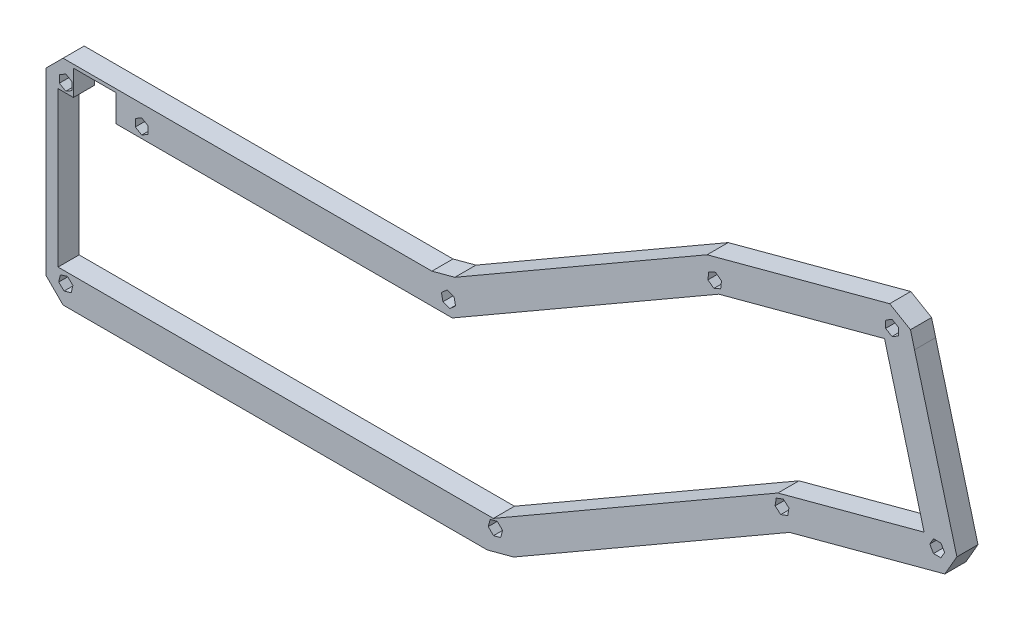
SolidWorks part; units mm, degrees
ref_plane "Plan de face" through (0, 0, 0) normal (0, 0, 1) x (1, 0, 0)
ref_plane "Plan de dessus" through (0, 0, 0) normal (0, 1, 0) x (1, 0, 0)
ref_plane "Plan de droite" through (0, 0, 0) normal (1, 0, 0) x (0, 0, -1)
sketch "Esquisse1" plane through (0, 0, 0) normal (0, 0, 1) x (1, 0, 0)
  line L0 (-73.9886, 18.0851) -> (-59.9886, 18.0851) construction
  line L1 (-73.9886, 37.0851) -> (-59.9886, 37.0851) construction
  line L2 (-73.9886, 37.0851) -> (-73.9886, 23.0851) construction
  line L3 (-73.9886, 23.0851) -> (-59.9886, 23.0851) construction
  line L4 (-59.9886, 37.0851) -> (-59.9886, 23.0851) construction
  line L5 (-73.9886, 18.0851) -> (-73.9886, 4.0851) construction
  line L6 (-73.9886, 4.0851) -> (-59.9886, 4.0851) construction
  line L7 (-59.9886, 18.0851) -> (-59.9886, 4.0851) construction
  line L8 (-73.9886, -0.9149) -> (-59.9886, -0.9149) construction
  line L9 (-73.9886, -0.9149) -> (-73.9886, -14.9149) construction
  line L10 (-73.9886, -14.9149) -> (-59.9886, -14.9149) construction
  line L11 (-59.9886, -0.9149) -> (-59.9886, -14.9149) construction
  line L12 (-73.9886, 37.0851) -> (-73.9886, 18.0851) construction
  line L13 (-54.9886, 18.0851) -> (-40.9886, 18.0851) construction
  line L14 (-54.9886, 37.0851) -> (-40.9886, 37.0851) construction
  line L15 (-54.9886, 37.0851) -> (-54.9886, 23.0851) construction
  line L16 (-54.9886, 23.0851) -> (-40.9886, 23.0851) construction
  line L17 (-40.9886, 37.0851) -> (-40.9886, 23.0851) construction
  line L18 (-54.9886, 18.0851) -> (-54.9886, 4.0851) construction
  line L19 (-54.9886, 4.0851) -> (-40.9886, 4.0851) construction
  line L20 (-40.9886, 18.0851) -> (-40.9886, 4.0851) construction
  line L21 (-54.9886, -0.9149) -> (-40.9886, -0.9149) construction
  line L22 (-54.9886, -0.9149) -> (-54.9886, -14.9149) construction
  line L23 (-54.9886, -14.9149) -> (-40.9886, -14.9149) construction
  line L24 (-40.9886, -0.9149) -> (-40.9886, -14.9149) construction
  line L25 (-54.9886, 37.0851) -> (-54.9886, 18.0851) construction
  line L26 (-35.9886, 18.0851) -> (-21.9886, 18.0851) construction
  line L27 (-35.9886, 37.0851) -> (-21.9886, 37.0851) construction
  line L28 (-35.9886, 37.0851) -> (-35.9886, 23.0851) construction
  line L29 (-35.9886, 23.0851) -> (-21.9886, 23.0851) construction
  line L30 (-21.9886, 37.0851) -> (-21.9886, 23.0851) construction
  line L31 (-35.9886, 18.0851) -> (-35.9886, 4.0851) construction
  line L32 (-35.9886, 4.0851) -> (-21.9886, 4.0851) construction
  line L33 (-21.9886, 18.0851) -> (-21.9886, 4.0851) construction
  line L34 (-35.9886, -0.9149) -> (-21.9886, -0.9149) construction
  line L35 (-35.9886, -0.9149) -> (-35.9886, -14.9149) construction
  line L36 (-35.9886, -14.9149) -> (-21.9886, -14.9149) construction
  line L37 (-21.9886, -0.9149) -> (-21.9886, -14.9149) construction
  line L38 (-35.9886, 37.0851) -> (-35.9886, 18.0851) construction
  line L39 (-16.9886, 18.0851) -> (-2.9886, 18.0851) construction
  line L40 (-16.9886, 37.0851) -> (-2.9886, 37.0851) construction
  line L41 (-16.9886, 37.0851) -> (-16.9886, 23.0851) construction
  line L42 (-16.9886, 23.0851) -> (-2.9886, 23.0851) construction
  line L43 (-2.9886, 37.0851) -> (-2.9886, 23.0851) construction
  line L44 (-16.9886, 18.0851) -> (-16.9886, 4.0851) construction
  line L45 (-16.9886, 4.0851) -> (-2.9886, 4.0851) construction
  line L46 (-2.9886, 18.0851) -> (-2.9886, 4.0851) construction
  line L47 (-16.9886, -0.9149) -> (-2.9886, -0.9149) construction
  line L48 (-16.9886, -0.9149) -> (-16.9886, -14.9149) construction
  line L49 (-16.9886, -14.9149) -> (-2.9886, -14.9149) construction
  line L50 (-2.9886, -0.9149) -> (-2.9886, -14.9149) construction
  line L51 (-16.9886, 37.0851) -> (-16.9886, 18.0851) construction
  line L52 (2.0114, 18.0851) -> (16.0114, 18.0851) construction
  line L53 (2.0114, 37.0851) -> (16.0114, 37.0851) construction
  line L54 (2.0114, 37.0851) -> (2.0114, 23.0851) construction
  line L55 (2.0114, 23.0851) -> (16.0114, 23.0851) construction
  line L56 (16.0114, 37.0851) -> (16.0114, 23.0851) construction
  line L57 (2.0114, 18.0851) -> (2.0114, 4.0851) construction
  line L58 (2.0114, 4.0851) -> (16.0114, 4.0851) construction
  line L59 (16.0114, 18.0851) -> (16.0114, 4.0851) construction
  line L60 (2.0114, -0.9149) -> (16.0114, -0.9149) construction
  line L61 (2.0114, -0.9149) -> (2.0114, -14.9149) construction
  line L62 (2.0114, -14.9149) -> (16.0114, -14.9149) construction
  line L63 (16.0114, -0.9149) -> (16.0114, -14.9149) construction
  line L64 (2.0114, 37.0851) -> (2.0114, 18.0851) construction
  line L65 (21.0114, 18.0851) -> (35.0114, 18.0851) construction
  line L66 (21.0114, 37.0851) -> (35.0114, 37.0851) construction
  line L67 (21.0114, 37.0851) -> (21.0114, 23.0851) construction
  line L68 (21.0114, 23.0851) -> (35.0114, 23.0851) construction
  line L69 (35.0114, 37.0851) -> (35.0114, 23.0851) construction
  line L70 (21.0114, 18.0851) -> (21.0114, 4.0851) construction
  line L71 (21.0114, 4.0851) -> (35.0114, 4.0851) construction
  line L72 (35.0114, 18.0851) -> (35.0114, 4.0851) construction
  line L73 (21.0114, -0.9149) -> (35.0114, -0.9149) construction
  line L74 (21.0114, -0.9149) -> (21.0114, -14.9149) construction
  line L75 (21.0114, -14.9149) -> (35.0114, -14.9149) construction
  line L76 (35.0114, -0.9149) -> (35.0114, -14.9149) construction
  line L77 (21.0114, 37.0851) -> (21.0114, 18.0851) construction
  line L78 (40.0114, 18.0851) -> (54.0114, 18.0851) construction
  line L79 (40.0114, 37.0851) -> (54.0114, 37.0851) construction
  line L80 (40.0114, 37.0851) -> (40.0114, 23.0851) construction
  line L81 (40.0114, 23.0851) -> (54.0114, 23.0851) construction
  line L82 (54.0114, 37.0851) -> (54.0114, 23.0851) construction
  line L83 (40.0114, 18.0851) -> (40.0114, 4.0851) construction
  line L84 (40.0114, 4.0851) -> (54.0114, 4.0851) construction
  line L85 (54.0114, 18.0851) -> (54.0114, 4.0851) construction
  line L86 (40.0114, -0.9149) -> (54.0114, -0.9149) construction
  line L87 (40.0114, -0.9149) -> (40.0114, -14.9149) construction
  line L88 (40.0114, -14.9149) -> (54.0114, -14.9149) construction
  line L89 (54.0114, -0.9149) -> (54.0114, -14.9149) construction
  line L90 (40.0114, 37.0851) -> (40.0114, 18.0851) construction
  line L91 (-73.9886, 18.0851) -> (-54.9886, 18.0851) construction
  line L92 (56.0114, 20.0851) -> (56.7532, 18.8002) construction
  line L93 (38.0114, 39.0851) -> (56.0114, 39.0851) construction
  line L94 (56.0114, 39.0851) -> (56.0114, 21.0851) construction
  line L95 (38.0114, 21.0851) -> (56.0114, 21.0851) construction
  line L96 (38.0114, 39.0851) -> (38.0114, 21.0851) construction
  line L97 (19.0114, 39.0851) -> (37.0114, 39.0851) construction
  line L98 (37.0114, 39.0851) -> (37.0114, 21.0851) construction
  line L99 (19.0114, 21.0851) -> (37.0114, 21.0851) construction
  line L100 (19.0114, 39.0851) -> (19.0114, 21.0851) construction
  line L101 (79.4363, 55.512) -> (88.4363, 39.9235) construction
  line L102 (88.4363, 39.9235) -> (72.8478, 30.9235) construction
  line L103 (63.8478, 46.512) -> (72.8478, 30.9235) construction
  line L104 (79.4363, 55.512) -> (63.8478, 46.512) construction
  line L105 (62.9818, 46.012) -> (71.9818, 30.4235) construction
  line L106 (71.9818, 30.4235) -> (56.3933, 21.4235) construction
  line L107 (47.3933, 37.012) -> (56.3933, 21.4235) construction
  line L108 (62.9818, 46.012) -> (47.3933, 37.012) construction
  line L109 (164.5845, 60.0309) -> (148.9961, 51.0309) construction
  line L110 (62.2497, 43.2799) -> (71.7497, 26.8254) construction
  line L111 (78.7042, 52.7799) -> (88.2042, 36.3254) construction
  line L112 (95.1587, 62.2799) -> (104.6587, 45.8254) construction
  line L113 (111.6132, 71.7799) -> (121.1132, 55.3254) construction
  line L114 (128.0677, 81.2799) -> (137.5677, 64.8254) construction
  line L115 (144.5221, 90.7799) -> (154.0221, 74.3254) construction
  line L116 (148.9961, 51.0309) -> (157.6657, 36.0146) construction
  line L117 (69.1254, 3.371) -> (76.1254, -8.7534) construction
  line L118 (88.2497, -1.7534) -> (76.1254, -8.7534) construction
  line L119 (81.2497, 10.371) -> (88.2497, -1.7534) construction
  line L120 (81.2497, 10.371) -> (69.1254, 3.371) construction
  line L121 (59.6254, 19.8254) -> (66.6254, 7.7011) construction
  line L122 (78.7497, 14.7011) -> (66.6254, 7.7011) construction
  line L123 (71.7497, 26.8254) -> (78.7497, 14.7011) construction
  line L124 (50.1254, 36.2799) -> (57.1254, 24.1556) construction
  line L125 (69.2497, 31.1556) -> (57.1254, 24.1556) construction
  line L126 (62.2497, 43.2799) -> (69.2497, 31.1556) construction
  line L127 (62.2497, 43.2799) -> (50.1254, 36.2799) construction
  line L128 (71.7497, 26.8254) -> (59.6254, 19.8254) construction
  line L129 (85.5799, 12.871) -> (92.5799, 0.7466) construction
  line L130 (104.7042, 7.7466) -> (92.5799, 0.7466) construction
  line L131 (97.7042, 19.871) -> (104.7042, 7.7466) construction
  line L132 (97.7042, 19.871) -> (85.5799, 12.871) construction
  line L133 (76.0799, 29.3254) -> (83.0799, 17.2011) construction
  line L134 (95.2042, 24.2011) -> (83.0799, 17.2011) construction
  line L135 (88.2042, 36.3254) -> (95.2042, 24.2011) construction
  line L136 (66.5799, 45.7799) -> (73.5799, 33.6556) construction
  line L137 (85.7042, 40.6556) -> (73.5799, 33.6556) construction
  line L138 (78.7042, 52.7799) -> (85.7042, 40.6556) construction
  line L139 (78.7042, 52.7799) -> (66.5799, 45.7799) construction
  line L140 (88.2042, 36.3254) -> (76.0799, 29.3254) construction
  line L141 (102.0343, 22.371) -> (109.0343, 10.2466) construction
  line L142 (121.1587, 17.2466) -> (109.0343, 10.2466) construction
  line L143 (114.1587, 29.371) -> (121.1587, 17.2466) construction
  line L144 (114.1587, 29.371) -> (102.0343, 22.371) construction
  line L145 (92.5343, 38.8254) -> (99.5343, 26.7011) construction
  line L146 (111.6587, 33.7011) -> (99.5343, 26.7011) construction
  line L147 (104.6587, 45.8254) -> (111.6587, 33.7011) construction
  line L148 (83.0343, 55.2799) -> (90.0343, 43.1556) construction
  line L149 (102.1587, 50.1556) -> (90.0343, 43.1556) construction
  line L150 (95.1587, 62.2799) -> (102.1587, 50.1556) construction
  line L151 (95.1587, 62.2799) -> (83.0343, 55.2799) construction
  line L152 (104.6587, 45.8254) -> (92.5343, 38.8254) construction
  line L153 (118.4888, 31.871) -> (125.4888, 19.7466) construction
  line L154 (137.6132, 26.7466) -> (125.4888, 19.7466) construction
  line L155 (130.6132, 38.871) -> (137.6132, 26.7466) construction
  line L156 (130.6132, 38.871) -> (118.4888, 31.871) construction
  line L157 (108.9888, 48.3254) -> (115.9888, 36.2011) construction
  line L158 (128.1132, 43.2011) -> (115.9888, 36.2011) construction
  line L159 (121.1132, 55.3254) -> (128.1132, 43.2011) construction
  line L160 (99.4888, 64.7799) -> (106.4888, 52.6556) construction
  line L161 (118.6132, 59.6556) -> (106.4888, 52.6556) construction
  line L162 (111.6132, 71.7799) -> (118.6132, 59.6556) construction
  line L163 (111.6132, 71.7799) -> (99.4888, 64.7799) construction
  line L164 (121.1132, 55.3254) -> (108.9888, 48.3254) construction
  line L165 (134.9433, 41.371) -> (141.9433, 29.2466) construction
  line L166 (154.0677, 36.2466) -> (141.9433, 29.2466) construction
  line L167 (147.0677, 48.371) -> (154.0677, 36.2466) construction
  line L168 (147.0677, 48.371) -> (134.9433, 41.371) construction
  line L169 (125.4433, 57.8254) -> (132.4433, 45.7011) construction
  line L170 (144.5677, 52.7011) -> (132.4433, 45.7011) construction
  line L171 (137.5677, 64.8254) -> (144.5677, 52.7011) construction
  line L172 (115.9433, 74.2799) -> (122.9433, 62.1556) construction
  line L173 (135.0677, 69.1556) -> (122.9433, 62.1556) construction
  line L174 (128.0677, 81.2799) -> (135.0677, 69.1556) construction
  line L175 (128.0677, 81.2799) -> (115.9433, 74.2799) construction
  line L176 (137.5677, 64.8254) -> (125.4433, 57.8254) construction
  line L177 (151.7281, 50.2988) -> (158.3978, 38.7466) construction
  line L178 (170.5221, 45.7466) -> (158.3978, 38.7466) construction
  line L179 (163.8525, 57.2988) -> (170.5221, 45.7466) construction
  line L180 (163.8525, 57.2988) -> (151.7281, 50.2988) construction
  line L181 (141.8978, 67.3254) -> (148.8978, 55.2011) construction
  line L182 (161.0221, 62.2011) -> (148.8978, 55.2011) construction
  line L183 (154.0221, 74.3254) -> (161.0221, 62.2011) construction
  line L184 (132.3978, 83.7799) -> (139.3978, 71.6556) construction
  line L185 (151.5221, 78.6556) -> (139.3978, 71.6556) construction
  line L186 (144.5221, 90.7799) -> (151.5221, 78.6556) construction
  line L187 (144.5221, 90.7799) -> (132.3978, 83.7799) construction
  line L188 (154.0221, 74.3254) -> (141.8978, 67.3254) construction
  line L189 (173.2542, 45.0146) -> (157.6657, 36.0146) construction
  line L190 (164.5845, 60.0309) -> (173.2542, 45.0146) construction
  line L191 (178.3169, 34.0986) -> (169.0534, 56.4627) construction
  line L192 (169.6903, 62.1458) -> (174.1781, 45.3972) construction
  line L193 (174.1781, 45.3972) -> (191.5647, 50.056) construction
  line L194 (187.077, 66.8045) -> (191.5647, 50.056) construction
  line L195 (162.1337, 98.0749) -> (167.0513, 79.7223) construction
  line L196 (169.6903, 62.1458) -> (187.077, 66.8045) construction
  line L197 (167.0513, 79.7223) -> (180.5742, 83.3457) construction
  line L198 (162.1337, 98.0749) -> (175.6567, 101.6983) construction
  line L199 (162.1337, 98.0749) -> (165.7572, 84.5519) construction
  line L200 (165.7572, 84.5519) -> (179.2801, 88.1754) construction
  line L201 (175.6567, 101.6983) -> (179.2801, 88.1754) construction
  line L202 (167.0513, 79.7223) -> (170.6747, 66.1993) construction
  line L203 (170.6747, 66.1993) -> (184.1977, 69.8228) construction
  line L204 (180.5742, 83.3457) -> (184.1977, 69.8228) construction
  line L205 (172.1398, 60.7315) -> (185.6628, 64.355) construction
  line L206 (172.1398, 60.7315) -> (175.5923, 47.8467) construction
  line L207 (175.5923, 47.8467) -> (189.1152, 51.4702) construction
  line L208 (185.6628, 64.355) -> (189.1152, 51.4702) construction
  line L209 (185.4038, 84.6398) -> (198.9268, 88.2633) construction
  line L210 (180.4863, 102.9924) -> (194.0092, 106.6159) construction
  line L211 (180.4863, 102.9924) -> (184.1097, 89.4695) construction
  line L212 (184.1097, 89.4695) -> (197.6327, 93.0929) construction
  line L213 (194.0092, 106.6159) -> (197.6327, 93.0929) construction
  line L214 (185.4038, 84.6398) -> (189.0273, 71.1169) construction
  line L215 (189.0273, 71.1169) -> (202.5503, 74.7403) construction
  line L216 (198.9268, 88.2633) -> (202.5503, 74.7403) construction
  line L217 (190.4924, 65.6491) -> (204.0154, 69.2726) construction
  line L218 (190.4924, 65.6491) -> (193.9449, 52.7643) construction
  line L219 (193.9449, 52.7643) -> (207.4678, 56.3878) construction
  line L220 (204.0154, 69.2726) -> (207.4678, 56.3878) construction
  line L221 (188.0429, 67.0633) -> (192.5307, 50.3148) construction
  line L222 (192.5307, 50.3148) -> (209.9173, 54.9735) construction
  line L223 (205.4296, 71.7221) -> (209.9173, 54.9735) construction
  line L224 (180.4863, 102.9924) -> (185.4038, 84.6398) construction
  line L225 (188.0429, 67.0633) -> (205.4296, 71.7221) construction
  line L226 (203.7564, 89.5574) -> (217.2794, 93.1809) construction
  line L227 (198.8389, 107.91) -> (212.3618, 111.5335) construction
  line L228 (198.8389, 107.91) -> (202.4623, 94.387) construction
  line L229 (202.4623, 94.387) -> (215.9853, 98.0105) construction
  line L230 (212.3618, 111.5335) -> (215.9853, 98.0105) construction
  line L231 (203.7564, 89.5574) -> (207.3799, 76.0344) construction
  line L232 (207.3799, 76.0344) -> (220.9029, 79.6579) construction
  line L233 (217.2794, 93.1809) -> (220.9029, 79.6579) construction
  line L234 (208.845, 70.5667) -> (222.368, 74.1901) construction
  line L235 (208.845, 70.5667) -> (212.2975, 57.6819) construction
  line L236 (212.2975, 57.6819) -> (225.8204, 61.3053) construction
  line L237 (222.368, 74.1901) -> (225.8204, 61.3053) construction
  line L238 (206.3955, 71.9809) -> (210.8833, 55.2324) construction
  line L239 (210.8833, 55.2324) -> (228.2699, 59.8911) construction
  line L240 (223.7822, 76.6396) -> (228.2699, 59.8911) construction
  line L241 (198.8389, 107.91) -> (203.7564, 89.5574) construction
  line L242 (206.3955, 71.9809) -> (223.7822, 76.6396) construction
  line L243 (167.0513, 79.7223) -> (185.4038, 84.6398) construction
  line L244 (38.0114, 20.0851) -> (56.0114, 20.0851) construction
  line L245 (56.0114, 20.0851) -> (56.0114, 2.0851) construction
  line L246 (38.0114, 2.0851) -> (56.0114, 2.0851) construction
  line L247 (38.0114, 20.0851) -> (38.0114, 2.0851) construction
  line L248 (72.4818, 29.5575) -> (56.8933, 20.5575) construction
  line L249 (56.8933, 20.5575) -> (65.8933, 4.969) construction
  line L250 (81.4818, 13.969) -> (65.8933, 4.969) construction
  line L251 (72.4818, 29.5575) -> (81.4818, 13.969) construction
  line L252 (56.8933, 20.5575) -> (57.6111, 19.3142) construction
  line L253 (164.6018, 81.1365) -> (169.2605, 63.7498) construction
  line L254 (169.2605, 63.7498) -> (186.6472, 68.4086) construction
  line L255 (181.9884, 85.7952) -> (186.6472, 68.4086) construction
  line L256 (164.6018, 81.1365) -> (181.9884, 85.7952) construction
  line L257 (154.7542, 77.0575) -> (163.7542, 61.469) construction
  line L258 (163.7542, 61.469) -> (148.1657, 52.469) construction
  line L259 (139.1657, 68.0575) -> (148.1657, 52.469) construction
  line L260 (154.7542, 77.0575) -> (139.1657, 68.0575) construction
  line L261 (196.3894, 109.3242) -> (213.776, 113.983) construction
  line L262 (-94.7538, 35.7952) -> (-76.7538, 35.7952) construction
  line L263 (-94.7538, 35.7952) -> (-94.7538, 2.7952) construction
  line L264 (-94.7538, 2.7952) -> (-76.7538, 2.7952) construction
  line L265 (-76.7538, 35.7952) -> (-76.7538, 2.7952) construction
  line L266 (213.776, 113.983) -> (218.4348, 96.5963) construction
  line L267 (201.0481, 91.9375) -> (218.4348, 96.5963) construction
  line L268 (196.3894, 109.3242) -> (201.0481, 91.9375) construction
  line L269 (-75.9886, -16.9149) -> (-57.9886, -16.9149) construction
  line L270 (-57.9886, 1.0851) -> (-57.9886, -16.9149) construction
  line L271 (-75.9886, 1.0851) -> (-57.9886, 1.0851) construction
  line L272 (-75.9886, 1.0851) -> (-75.9886, -16.9149) construction
  line L273 (38.0114, -16.9149) -> (56.0114, -16.9149) construction
  line L274 (56.0114, 1.0851) -> (56.0114, -16.9149) construction
  line L275 (38.0114, 1.0851) -> (56.0114, 1.0851) construction
  line L276 (38.0114, 1.0851) -> (38.0114, -16.9149) construction
  line L277 (-75.9886, 39.0851) -> (-57.9886, 39.0851) construction
  line L278 (-57.9886, 39.0851) -> (-57.9886, 21.0851) construction
  line L279 (-75.9886, 21.0851) -> (-57.9886, 21.0851) construction
  line L280 (-75.9886, 39.0851) -> (-75.9886, 21.0851) construction
  line L281 (145.2542, 93.512) -> (129.6657, 84.512) construction
  line L282 (129.6657, 84.512) -> (138.6657, 68.9235) construction
  line L283 (154.2542, 77.9235) -> (138.6657, 68.9235) construction
  line L284 (145.2542, 93.512) -> (154.2542, 77.9235) construction
  line L285 (223.4353, 116.5711) -> (228.0941, 99.1845) construction
  line L286 (148.2159, 106.7689) -> (211.1879, 123.6422) construction
  line L287 (177.5508, 35.9482) -> (235.6877, 51.5259) construction
  line L288 (177.5508, 35.9482) -> (72.9989, -24.4149) construction
  line L289 (-95.7538, -26.9149) -> (63.6687, -26.9149) construction
  line L290 (-100.7538, 35.7952) -> (-100.7538, -21.9149) construction
  line L291 (-75.9886, 49.0851) -> (43.3046, 49.0851) construction
  line L292 (148.2159, 106.7689) -> (52.6347, 51.5851) construction
  line L293 (-75.9886, 49.0851) -> (-57.9886, 49.0851) construction
  line L294 (140.2542, 102.1722) -> (124.6657, 93.1722) construction
  line L295 (193.8012, 118.9835) -> (211.1879, 123.6422) construction
  line L296 (213.4714, 45.5731) -> (230.8581, 50.2318) construction
  line L297 (38.0114, -26.9149) -> (38.0114, -85.4624) construction
  line L298 (178.2542, 36.3543) -> (162.6657, 27.3543) construction
  line L299 (38.0114, -26.9149) -> (56.0114, -26.9149) construction
  line L300 (-100.7538, 2.7952) -> (-100.7538, -38.0419) construction
  line L301 (-100.7538, 35.7952) -> (-100.7538, 2.7952) construction
  line L302 (-75.9886, 49.0851) -> (-95.7538, 49.0851) construction
  line L303 (-100.7538, 44.0851) -> (-100.7538, 35.7952) construction
  line L304 (211.1879, 123.6422) -> (216.0693, 124.9502) construction
  line L305 (222.1671, 121.4078) -> (223.4353, 116.5711) construction
  line L306 (228.0941, 99.1845) -> (239.2233, 57.6497) construction
  line L307 (216.0693, 124.9502) -> (222.1671, 121.4078) construction
  line L308 (235.6877, 51.5259) -> (239.2233, 57.6497) construction
  line L309 (63.6687, -26.9149) -> (72.9989, -24.4149) construction
  line L310 (52.6347, 51.5851) -> (43.3046, 49.0851) construction
  line L311 (-95.7538, 49.0851) -> (-100.7538, 44.0851) construction
  line L312 (-100.7538, -21.9149) -> (-95.7538, -26.9149) construction
  line L313 (-95.7538, 49.0851) -> (-95.7538, 44.0851) construction
  line L314 (-95.7538, 44.0851) -> (-100.7538, 44.0851) construction
  line L315 (-95.7538, -26.9149) -> (-95.7538, -21.9149) construction
  line L316 (68.3338, -25.6649) -> (67.0397, -20.8353) construction
  line L317 (47.9697, 50.3351) -> (49.2637, 45.5055) construction
  line L318 (177.5508, 35.9482) -> (175.6374, 40.5676) construction
  line L319 (148.2159, 106.7689) -> (150.1293, 102.1495) construction
  line L320 (239.2233, 57.6497) -> (234.4455, 56.3695) construction
  line L321 (216.0693, 124.9502) -> (217.3634, 120.1206) construction
  line L322 (-75.9886, 49.5851) -> (43.2388, 49.5851) construction
  line L323 (52.4417, 52.051) -> (43.2388, 49.5851) construction
  line L324 (148.0229, 107.2348) -> (52.4417, 52.051) construction
  line L325 (148.0229, 107.2348) -> (211.0584, 124.1252) construction
  line L326 (211.0584, 124.1252) -> (216.1407, 125.487) construction
  line L327 (216.1407, 125.487) -> (222.598, 121.7357) construction
  line L328 (222.598, 121.7357) -> (223.9186, 116.6993) construction
  line L329 (223.9186, 116.6993) -> (228.577, 99.3139) construction
  line L330 (228.577, 99.3139) -> (239.7598, 57.579) construction
  line L331 (236.0172, 51.0966) -> (239.7598, 57.579) construction
  line L332 (177.7438, 35.4823) -> (236.0172, 51.0966) construction
  line L333 (177.7438, 35.4823) -> (73.1918, -24.8808) construction
  line L334 (63.7346, -27.4149) -> (73.1918, -24.8808) construction
  line L335 (-95.9609, -27.4149) -> (63.7346, -27.4149) construction
  line L336 (-101.2538, -22.122) -> (-95.9609, -27.4149) construction
  line L337 (-101.2538, 35.7952) -> (-101.2538, -22.122) construction
  line L338 (-101.2538, 44.2922) -> (-101.2538, 35.7952) construction
  line L339 (-95.9609, 49.5851) -> (-101.2538, 44.2922) construction
  line L340 (-75.9886, 49.5851) -> (-76.7538, 49.5851) construction
  line L341 (2.0114, 40.0851) -> (52.7161, 40.0851)
  line L342 (151.6898, 98.3823) -> (50.7161, 40.0851)
  line L343 (-95.7538, 44.0851) -> (-63.3184, 44.0851) construction
  line L344 (-98.6986, -17.9149) -> (66.2572, -17.9149)
  line L345 (174.0769, 44.3349) -> (66.2572, -17.9149)
  line L346 (174.0769, 44.3349) -> (229.4947, 59.184)
  line L347 (214.4832, 115.2077) -> (229.4947, 59.184)
  line L348 (151.6898, 98.3823) -> (214.4832, 115.2077)
  line L349 (225.2657, 74.9666) -> (228.7182, 62.0818) construction
  line L350 (176.3687, 44.949) -> (189.8917, 48.5724) construction
  line L351 (89.7497, -4.3515) -> (77.6254, -11.3515) construction
  line L352 (-54.9886, -17.9149) -> (-40.9886, -17.9149) construction
  line L353 (-92.8618, 49.5851) -> (-76.7538, 49.5851) construction
  line L354 (2.0114, 40.0851) -> (16.0114, 40.0851) construction
  line L355 (77.2042, 55.378) -> (65.0799, 48.378) construction
  line L356 (179.7098, 105.8902) -> (193.2328, 109.5137) construction
  line L357 (2.0114, 40.0851) -> (-76.7538, 40.0851)
  line L358 (-76.7538, 40.0851) -> (-76.7538, 54.5851) construction
  line L359 (-92.8618, 54.5851) -> (-76.7538, 54.5851) construction
  line L360 (-98.6986, 40.6556) -> (-94.8608, 40.6556)
  line L361 (-94.8608, 40.6556) -> (-92.8618, 40.6556)
  line L362 (-94.8608, 49.5851) -> (-95.9609, 49.5851) construction
  line L363 (-66.9886, 37.0851) -> (-66.9886, 49.5851) construction
  line L364 (-75.9886, 49.5851) -> (-95.9609, 49.5851) construction
  line L365 (-92.8618, 40.6556) -> (-92.8618, 54.5851) construction
  line L366 (-76.7538, 39.0851) -> (-97.0101, 39.0851) construction
  line L367 (-76.7538, 39.0851) -> (-76.7538, 1.0851) construction
  line L368 (-76.7538, 1.0851) -> (-97.0101, 1.0851) construction
  line L369 (-97.0101, 39.0851) -> (-97.0101, 1.0851) construction
  line L370 (-92.8618, 49.5851) -> (-94.8608, 49.5851) construction
  line L371 (-98.6986, 40.6556) -> (-98.6986, -17.9149)
  line L372 (-75.9886, 54.5851) -> (-76.7538, 54.5851) construction
  line L373 (-75.9886, 54.5851) -> (42.5805, 54.5851) construction
  line L374 (50.5118, 56.7103) -> (42.5805, 54.5851) construction
  line L375 (146.093, 111.8941) -> (50.5118, 56.7103) construction
  line L376 (146.093, 111.8941) -> (209.7644, 128.9548) construction
  line L377 (209.7644, 128.9548) -> (216.8547, 130.8547) construction
  line L378 (216.8547, 130.8547) -> (226.9072, 125.0148) construction
  line L379 (226.9072, 125.0148) -> (228.7517, 117.9804) construction
  line L380 (228.7517, 117.9804) -> (233.4066, 100.608) construction
  line L381 (233.4066, 100.608) -> (245.1255, 56.8726) construction
  line L382 (239.3118, 46.803) -> (245.1255, 56.8726) construction
  line L383 (179.6737, 30.823) -> (239.3118, 46.803) construction
  line L384 (179.6737, 30.823) -> (75.1218, -29.5401) construction
  line L385 (64.3928, -32.4149) -> (75.1218, -29.5401) construction
  line L386 (-98.0319, -32.4149) -> (64.3928, -32.4149) construction
  line L387 (-106.2538, -24.1931) -> (-98.0319, -32.4149) construction
  line L388 (-106.2538, 35.7952) -> (-106.2538, -24.1931) construction
  line L389 (-106.2538, 46.3633) -> (-106.2538, 35.7952) construction
  line L390 (-98.0319, 54.5851) -> (-106.2538, 46.3633) construction
  line L391 (-94.8608, 54.5851) -> (-98.0319, 54.5851) construction
  line L392 (-92.8618, 54.5851) -> (-94.8608, 54.5851) construction
  line L393 (-92.8618, 50.2988) -> (-76.7538, 50.2988)
  line L394 (-76.7538, 54.5851) -> (-92.8618, 54.5851) construction
  line L395 (-76.7538, 51.5851) -> (-92.8618, 51.5851)
  line L396 (-92.8618, 51.5851) -> (-94.8608, 51.5851)
  line L397 (-94.8608, 51.5851) -> (-96.7893, 51.5851)
  line L398 (-96.7893, 51.5851) -> (-103.2538, 45.1206)
  line L399 (-103.2538, 45.1206) -> (-103.2538, 35.7952)
  line L400 (-103.2538, 35.7952) -> (-103.2538, -22.9504)
  line L401 (-103.2538, -22.9504) -> (-96.7893, -29.4149)
  line L402 (-96.7893, -29.4149) -> (63.9979, -29.4149)
  line L403 (63.9979, -29.4149) -> (73.9638, -26.7445)
  line L404 (178.5158, 33.6186) -> (73.9638, -26.7445)
  line L405 (178.5158, 33.6186) -> (237.335, 49.3791)
  line L406 (237.335, 49.3791) -> (241.9061, 57.2965)
  line L407 (230.5089, 99.8315) -> (241.9061, 57.2965)
  line L408 (225.8519, 117.2117) -> (230.5089, 99.8315)
  line L409 (224.3217, 123.0473) -> (225.8519, 117.2117)
  line L410 (216.4263, 127.634) -> (224.3217, 123.0473)
  line L411 (210.5408, 126.057) -> (216.4263, 127.634)
  line L412 (147.2509, 109.0986) -> (210.5408, 126.057)
  line L413 (147.2509, 109.0986) -> (51.6698, 53.9147)
  line L414 (51.6698, 53.9147) -> (42.9755, 51.5851)
  line L415 (-75.9886, 51.5851) -> (42.9755, 51.5851)
  line L416 (-75.9886, 51.5851) -> (-76.7538, 51.5851)
  line L417 (-76.7538, 48.6361) -> (-76.7538, 40.0851)
  line L418 (-92.8618, 48.6361) -> (-92.8618, 40.6556)
  line L419 (-76.7538, 50.2988) -> (-76.7538, 48.6361)
  line L420 (-92.8618, 50.2988) -> (-92.8618, 48.6361)
  line L421 (-97.4756, -23.6367) -> (-94.032, -20.1931) construction
  line L422 (-93.3188, 42.6793) -> (-93.3188, 45.491)
  line L423 (-93.3188, 45.491) -> (-95.7538, 46.8968)
  line L424 (-95.7538, 46.8968) -> (-98.1888, 45.491)
  line L425 (-98.1888, 45.491) -> (-98.1888, 42.6793)
  line L426 (-98.1888, 42.6793) -> (-95.7538, 41.2734)
  line L427 (-95.7538, 41.2734) -> (-93.3188, 42.6793)
  line L428 (-64.5536, 45.491) -> (-66.9886, 46.8968)
  line L429 (-66.9886, 46.8968) -> (-69.4236, 45.491)
  line L430 (-69.4236, 45.491) -> (-69.4236, 42.6793)
  line L431 (-69.4236, 42.6793) -> (-66.9886, 41.2734)
  line L432 (-66.9886, 41.2734) -> (-64.5536, 42.6793)
  line L433 (-64.5536, 42.6793) -> (-64.5536, 45.491)
  line L434 (51.9317, 44.6181) -> (51.3662, 47.3724)
  line L435 (51.3662, 47.3724) -> (48.6982, 48.2597)
  line L436 (48.6982, 48.2597) -> (46.5957, 46.3928)
  line L437 (46.5957, 46.3928) -> (47.1613, 43.6386)
  line L438 (47.1613, 43.6386) -> (49.8293, 42.7512)
  line L439 (49.8293, 42.7512) -> (51.9317, 44.6181)
  line L440 (152.7035, 103.2806) -> (150.4369, 104.9443)
  line L441 (150.4369, 104.9443) -> (147.8627, 103.8133)
  line L442 (147.8627, 103.8133) -> (147.5551, 101.0185)
  line L443 (147.5551, 101.0185) -> (149.8217, 99.3547)
  line L444 (149.8217, 99.3547) -> (152.3959, 100.4857)
  line L445 (152.3959, 100.4857) -> (152.7035, 103.2806)
  line L446 (219.7717, 118.6694) -> (219.8243, 121.4806)
  line L447 (219.8243, 121.4806) -> (217.416, 122.9318)
  line L448 (217.416, 122.9318) -> (214.9551, 121.5717)
  line L449 (214.9551, 121.5717) -> (214.9025, 118.7605)
  line L450 (214.9025, 118.7605) -> (217.3108, 117.3094)
  line L451 (217.3108, 117.3094) -> (219.7717, 118.6694)
  line L452 (237.2572, 56.3695) -> (235.8513, 58.8045)
  line L453 (235.8513, 58.8045) -> (233.0396, 58.8045)
  line L454 (233.0396, 58.8045) -> (231.6338, 56.3695)
  line L455 (231.6338, 56.3695) -> (233.0396, 53.9345)
  line L456 (233.0396, 53.9345) -> (235.8513, 53.9345)
  line L457 (235.8513, 53.9345) -> (237.2572, 56.3695)
  line L458 (178.2704, 41.554) -> (176.0996, 43.341)
  line L459 (176.0996, 43.341) -> (173.4666, 42.3546)
  line L460 (173.4666, 42.3546) -> (173.0044, 39.5812)
  line L461 (173.0044, 39.5812) -> (175.1751, 37.7942)
  line L462 (175.1751, 37.7942) -> (177.8081, 38.7806)
  line L463 (177.8081, 38.7806) -> (178.2704, 41.554)
  line L464 (69.7556, -20.1075) -> (67.7674, -18.1194)
  line L465 (67.7674, -18.1194) -> (65.0515, -18.8471)
  line L466 (65.0515, -18.8471) -> (64.3238, -21.563)
  line L467 (64.3238, -21.563) -> (66.312, -23.5512)
  line L468 (66.312, -23.5512) -> (69.0279, -22.8234)
  line L469 (69.0279, -22.8234) -> (69.7556, -20.1075)
  line L471 (-93.0572, -21.1185) -> (-95.0952, -19.1814)
  line L472 (-95.0952, -19.1814) -> (-97.7917, -19.9778)
  line L473 (-97.7917, -19.9778) -> (-98.4503, -22.7113)
  line L474 (-98.4503, -22.7113) -> (-96.4124, -24.6484)
  line L475 (-96.4124, -24.6484) -> (-93.7158, -23.852)
  line L476 (-93.7158, -23.852) -> (-93.0572, -21.1185)
  circle A0 centre (-95.7538, 44.0851) radius 1.5 construction
  circle A1 centre (-95.7538, -21.9149) radius 1.5 construction
  circle A2 centre (67.0397, -20.8353) radius 1.5 construction
  circle A3 centre (49.2637, 45.5055) radius 1.5 construction
  circle A4 centre (175.6374, 40.5676) radius 1.5 construction
  circle A5 centre (150.1293, 102.1495) radius 1.5 construction
  circle A6 centre (234.4455, 56.3695) radius 1.5 construction
  circle A7 centre (217.3634, 120.1206) radius 1.5 construction
  circle A8 centre (-66.9886, 44.0851) radius 1.5 construction
  circle A9 centre (-95.7538, 44.0851) radius 2.435 construction
  circle A10 centre (-66.9886, 44.0851) radius 2.435 construction
  circle A11 centre (49.2637, 45.5055) radius 2.435 construction
  circle A12 centre (150.1293, 102.1495) radius 2.435 construction
  circle A13 centre (217.3634, 120.1206) radius 2.435 construction
  circle A14 centre (234.4455, 56.3695) radius 2.435 construction
  circle A15 centre (175.6374, 40.5676) radius 2.435 construction
  circle A16 centre (67.0397, -20.8353) radius 2.435 construction
  circle A17 centre (-95.7538, -21.9149) radius 2.435 construction
  point P304 (48.3046, 49.0851)
  point P305 (240.5174, 52.82)
  point P308 (68.6687, -26.9149)
  point P309 (-100.7538, -26.9149)
  point P311 (-100.7538, 49.0851)
  point P312 (220.8989, 126.2443)
  point P505 (-95.7538, -21.9149)
  dimension "D32" = 3
  dimension "D33" = 5
  dimension "D40" = 5
  dimension "D41" = 5
  dimension "D42" = 5
  dimension "D43" = 5
  dimension "D44" = 0.5
  dimension "D53" = 3
  dimension "D47" = 5
  dimension "D1" = 14
  dimension "D2" = 14
  dimension "D4" = 19
  dimension "D6" = 19
  dimension "D7" = 30
  dimension "D10" = 1
  dimension "D11" = 2
  dimension "D13" = 0.5
  dimension "D15" = 2
  dimension "D12" = 7.5
  dimension "D14" = 19
  dimension "D18" = 2
  dimension "D20" = 18
  dimension "D21" = 33
  dimension "D22" = 2
  dimension "D54" = 4.87
  dimension "D55" = 4.87
  dimension "D56" = 4.87
  dimension "D57" = 4.87
  dimension "D58" = 4.87
  dimension "D59" = 4.87
  dimension "D60" = 4.87
  dimension "D61" = 4.87
  dimension "D62" = 4.87
  dimension "D63" = 4.87
  dimension "D8" = 2
  dimension "D9" = 2
  dimension "D16" = 2
  dimension "D19" = 2
  dimension "D23" = 2
  dimension "D24" = 10
  dimension "D25" = 10
  dimension "D26" = 10
  dimension "D27" = 10
  dimension "D28" = 10
  dimension "D29" = 6
  dimension "D30" = 10
  dimension "D31" = 10
  dimension "D45" = 3
  dimension "D46" = 3
  dimension "D48" = 3
  dimension "D49" = 3
  dimension "D50" = 3
  dimension "D51" = 3
  dimension "D52" = 3
  dimension "D3" = 3
  dimension "D5" = 7
  dimension "D17" = 3
extrude "Boss.-Extru.1" add sketch "Esquisse1" along normal blind 8 contours L362 L339 L338 L337 L336 L335 L334 L333 L332 L331 L330 L329 L328 L327 L326 L325 L324 L323 L322 L340 L358 L357 L341 L342 L348 L347 L346 L345 L344 L360 A7 A6 A5 A4 A3 A2 A1 A0 region at (-76.3712, 47.793, 0)
